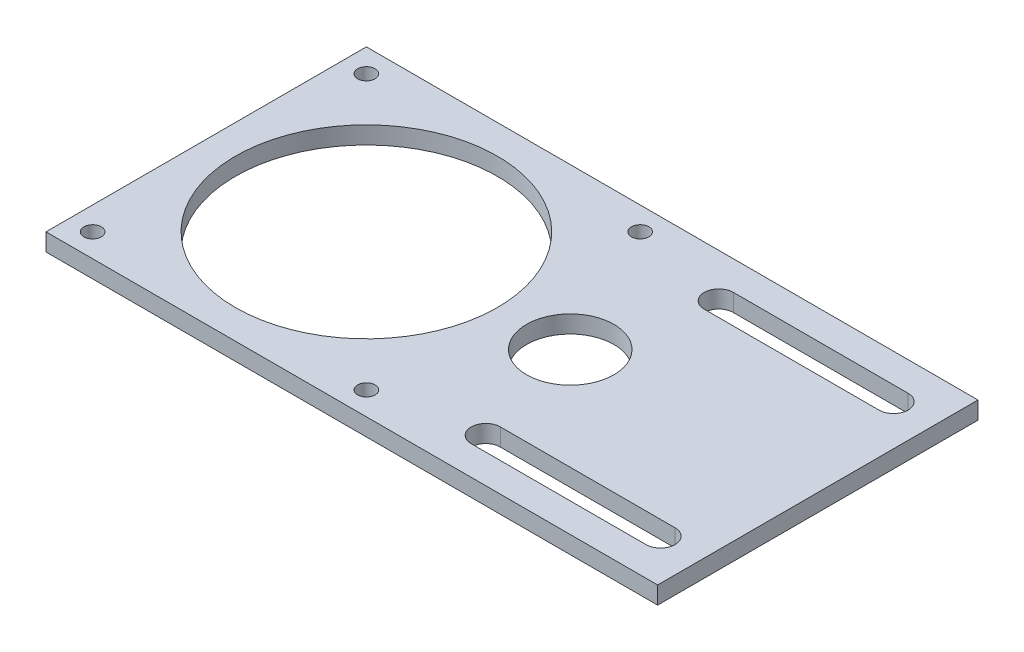
SolidWorks part; units mm, degrees
ref_plane "Front Plane" through (0, 0, 0) normal (0, 0, 1) x (1, 0, 0)
ref_plane "Top Plane" through (0, 0, 0) normal (0, 1, 0) x (1, 0, 0)
ref_plane "Right Plane" through (0, 0, 0) normal (1, 0, 0) x (0, 0, -1)
sketch "Sketch1" plane through (0, 0, 0) normal (0, 1, 0) x (1, 0, 0)
  line L0 (98, 47.5) -> (68, 47.5) construction
  line L1 (0, 0) -> (105, 0)
  line L2 (0, 0) -> (0, 55)
  line L3 (0, 55) -> (105, 55)
  line L4 (105, 0) -> (105, 55)
  line L5 (98, 45) -> (68, 45)
  line L6 (98, 50) -> (68, 50)
  line L7 (98, 7.5) -> (68, 7.5) construction
  line L8 (98, 5) -> (68, 5)
  line L9 (98, 10) -> (68, 10)
  circle A0 centre (27.5, 27.5) radius 22.5
  arc A1 (98, 45) -> (98, 50) centre (98, 47.5) ccw
  arc A2 (68, 50) -> (68, 45) centre (68, 47.5) ccw
  arc A3 (98, 5) -> (98, 10) centre (98, 7.5) ccw
  arc A4 (68, 10) -> (68, 5) centre (68, 7.5) ccw
  circle A5 centre (62.5, 27.5) radius 7.5
  circle A6 centre (4, 4) radius 1.5
  circle A7 centre (51, 4) radius 1.5
  circle A8 centre (51, 51) radius 1.5
  circle A9 centre (4, 51) radius 1.5
  point P9 (83, 47.5)
  point P17 (83, 7.5)
  dimension "D3" = 2
  dimension "D4" = 2
  dimension "D1" = 55
  dimension "D2" = 105
  dimension "D5" = 2
extrude "Boss-Extrude1" add sketch "Sketch1" along normal blind 3
ref_axis "Axis1" through (0, 3, -27.5) along (0.9996, -0.0286, 0)
